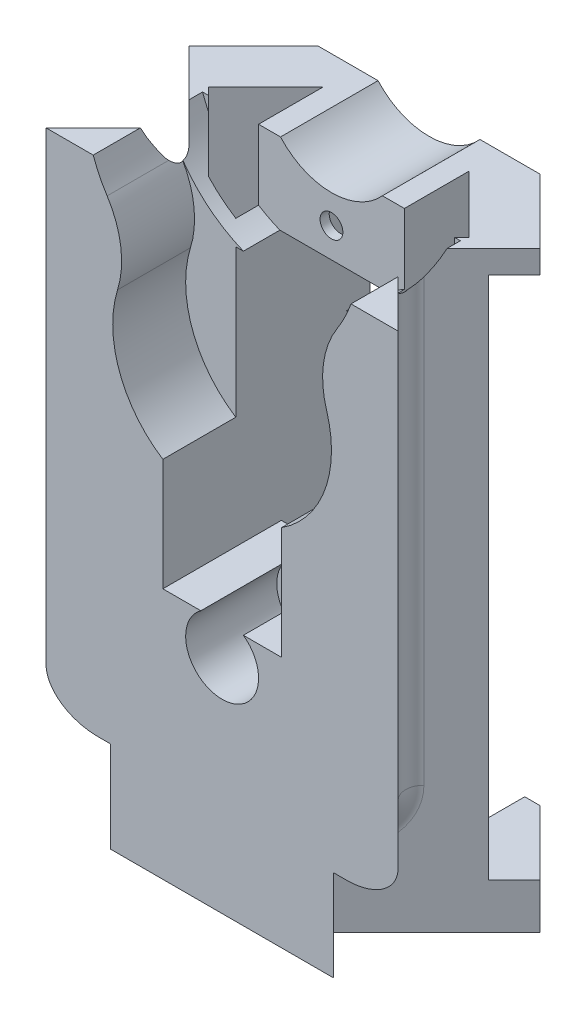
SolidWorks part; units mm, degrees
material "ABS"
ref_plane "前基準面" through (0, 0, 0) normal (0, 0, 1) x (1, 0, 0)
ref_plane "上基準面" through (0, 0, 0) normal (0, 1, 0) x (1, 0, 0)
ref_plane "右基準面" through (0, 0, 0) normal (1, 0, 0) x (0, 0, -1)
sketch "草圖1" plane through (0, 0, 0) normal (0, 1, 0) x (1, 0, 0)
  line L0 (0, 0) -> (24.34, 0)
  line L1 (24.34, 0) -> (34.67, -10.33)
  line L2 (34.67, -22.7) -> (-10.33, -22.7)
  line L3 (-10.33, -10.33) -> (0, 0)
  line L4 (-10.33, -22.7) -> (-10.33, -10.33)
  line L5 (34.67, -22.7) -> (34.67, -10.33)
  line L6 (12.17, 0) -> (12.17, -22.7) construction
  dimension "D1" = 22.7
  dimension "D2" = 24.34
  dimension "D3" = 45
extrude "填料-伸長1" add sketch "草圖1" along normal blind 65
ref_plane "平面1" through (0, 5, 0) normal (0, 1, 0) x (1, 0, 0)
sketch "草圖2" plane through (0, 5, 0) normal (0, 1, 0) x (1, 0, 0)
  line L0 (0, 0) -> (-22.7, -22.7)
  line L1 (-22.7, -22.7) -> (-17.0431, -22.7)
  line L2 (-10.33, -22.7) -> (34.67, -22.7) construction
  line L3 (-17.0431, -22.7) -> (5.6569, 0)
  line L4 (24.34, 0) -> (0, 0) construction
  line L5 (5.6569, 0) -> (0, 0)
  line L6 (-10.33, -22.7) -> (34.67, -22.7) construction
  line L8 (0, 0) -> (-10.33, -10.33) construction
  dimension "D1" = 4
extrude "除料-伸長1" cut sketch "草圖2" along normal blind 57.5
ref_plane "平面2" through (12.17, 0, 0) normal (-1, 0, 0) x (0, 0, 1)
mirror "鏡射1" about plane through (12.17, 0, 0) normal (-1, 0, 0) of "除料-伸長1"
sketch "草圖3" plane through (0, 0, 22.7) normal (0, 0, 1) x (1, 0, 0)
  line L0 (12.17, 65) -> (12.17, 0) construction
  line L1 (-10.33, 65) -> (34.67, 65) construction
  line L2 (-10.33, 0) -> (34.67, 0) construction
  point P6 (12.17, 50)
  point P8 (12.17, 70)
  dimension "D1" = 50
  dimension "D2" = 20
sketch "草圖4" plane through (0, 0, 22.7) normal (0, 0, 1) x (1, 0, 0)
  line L0 (12.17, 65) -> (12.17, 0) construction
  line L1 (5.67, 56.11) -> (18.67, 56.11)
  line L2 (5.67, 56.11) -> (5.67, 27.61)
  line L3 (5.67, 27.61) -> (18.67, 27.61)
  line L4 (18.67, 56.11) -> (18.67, 27.61)
  line L5 (5.67, 56.11) -> (18.67, 27.61) construction
  line L6 (5.67, 27.61) -> (18.67, 56.11) construction
  line L7 (12.17, 59.36) -> (12.17, 56.11) construction
  line L8 (12.17, 24.36) -> (12.17, 27.61) construction
  circle A0 centre (12.17, 59.36) radius 1.25
  circle A1 centre (12.17, 24.36) radius 1.25
  point P0 (12.17, 41.86)
  dimension "D5" = 2.5
  dimension "D1" = 28.5
  dimension "D2" = 13
  dimension "D3" = 6.11
  dimension "D4" = 35
extrude "除料-伸長2" cut sketch "草圖4" against normal blind 13
sketch "草圖9" plane through (0, 0, 9.7) normal (0, 0, 1) x (1, 0, 0)
  line L0 (12.17, 65) -> (12.17, 0) construction
  line L1 (5.67, 61.06) -> (18.67, 61.06)
  line L2 (5.67, 61.06) -> (5.67, 22.66)
  line L3 (5.67, 22.66) -> (18.67, 22.66)
  line L4 (18.67, 61.06) -> (18.67, 22.66)
  line L5 (5.67, 61.06) -> (18.67, 22.66) construction
  line L6 (5.67, 22.66) -> (18.67, 61.06) construction
  line L7 (18.67, 27.61) -> (18.67, 56.11) construction
  line L9 (18.67, 27.61) -> (18.67, 56.11) construction
  point P0 (12.17, 41.86)
  point P13 (18.67, 41.86)
  point P14 (18.67, 41.86)
  dimension "D1" = 38.4
extrude "除料-伸長6" cut sketch "草圖9" against normal through all
sketch "草圖10" plane through (0, 0, 0) normal (0, -1, 0) x (1, 0, 0)
  line L0 (24.34, 0) -> (0, 0) construction
  line L1 (20.67, 3) -> (3.67, 3)
  line L2 (22.67, 5) -> (22.67, 10)
  line L3 (22.67, 10) -> (1.67, 10)
  line L4 (1.67, 5) -> (1.67, 10)
  line L5 (12.17, 2.75) -> (12.17, -2.75) construction
  line L6 (22.67, 5) -> (20.67, 3)
  line L7 (3.67, 3) -> (1.67, 5)
  point P0 (22.67, 3)
  point P3 (1.67, 3)
  point P8 (12.17, 3)
  dimension "D1" = 21
  dimension "D2" = 3
  dimension "D3" = 7
extrude "除料-伸長7" cut sketch "草圖10" against normal blind 18
sketch "草圖13" plane through (0, 0, 0) normal (0, -1, 0) x (1, 0, 0)
  line L0 (1.67, 10) -> (1.67, 5) construction
  line L1 (22.67, 10) -> (1.67, 10)
  line L2 (22.67, 10) -> (22.67, 15)
  line L3 (22.67, 15) -> (1.67, 15)
  line L4 (1.67, 10) -> (1.67, 15)
extrude "除料-伸長10" cut sketch "草圖13" against normal blind 18
sketch "草圖11" plane through (0, 0, 0) normal (0, -1, 0) x (1, 0, 0)
  line L0 (-9.5579, 4.5842) -> (-25.1143, 20.1405)
  line L1 (-9.5579, 4.5842) -> (0.7071, 14.8492)
  line L2 (-25.1143, 20.1405) -> (-14.8492, 30.4056)
  line L3 (0.7071, 14.8492) -> (-14.8492, 30.4056)
  line L4 (0, 0) -> (-10.33, 10.33) construction
  line L7 (0, 0) -> (-10.33, 10.33) construction
  dimension "D2" = 22
  dimension "D3" = 11
  dimension "D4" = 10
extrude "除料-伸長8" cut sketch "草圖11" against normal through all
sketch "草圖12" plane through (0, 0, 0) normal (0, -1, 0) x (1, 0, 0)
  line L0 (-4.2426, 9.8995) -> (-19.799, 25.4558)
  line L1 (-4.2426, 9.8995) -> (4.2426, 18.3848)
  line L2 (-19.799, 25.4558) -> (-11.3137, 33.9411)
  line L3 (4.2426, 18.3848) -> (-11.3137, 33.9411)
  line L5 (-7.0711, 7.0711) -> (0.7071, 14.8492) construction
  line L7 (0.7071, 14.8492) -> (-7.1437, 22.7) construction
  dimension "D1" = 12
  dimension "D2" = 22
  dimension "D3" = 7
extrude "除料-伸長9" cut sketch "草圖12" against normal blind 10
fillet "圓角1" radius 4 1 edges at (-3.2183, 10, 18.7746)
mirror "鏡射3" about plane through (12.17, 0, 0) normal (-1, 0, 0) of "圓角1", "除料-伸長9", "除料-伸長8"
sketch "草圖21" plane through (0, 0, 0) normal (0, 0, -1) x (-1, 0, 0)
  line L0 (-1.67, 18) -> (-1.67, 0) construction
  line L1 (-22.67, 0) -> (-1.67, 0)
  line L2 (-22.67, 0) -> (-22.67, 14)
  line L3 (-22.67, 14) -> (-1.67, 14)
  line L4 (-1.67, 0) -> (-1.67, 14)
  line L7 (-24.34, 0) -> (0, 0) construction
  line L8 (-22.67, 5) -> (-22.67, 18) construction
  dimension "D1" = 14
extrude "除料-伸長17" cut sketch "草圖21" against normal blind 8
chamfer "導角2" [suppressed] distance 4 angle 45
sketch "草圖17" plane through (2.8284, 0, 2.8284) normal (-0.7071, 0, -0.7071) x (-0.7071, 0, 0.7071)
  line L1 (1.6383, 14) -> (21.437, 14)
  line L2 (1.6383, 14) -> (1.6383, 5)
  line L3 (1.6383, 5) -> (21.437, 5)
  line L4 (21.437, 14) -> (21.437, 5)
  line L5 (1.6383, 5) -> (1.6383, 14) construction
  line L6 (1.6383, 14) -> (-4, 14) construction
  dimension "D1" = 9
extrude "除料-伸長13" cut sketch "草圖17" against normal blind 3
sketch "草圖18" plane through (0, 0, 15) normal (0, 0, 1) x (1, 0, 0)
  line L0 (-0.0726, 0) -> (24.4126, 0) construction
  line L1 (19.17, 0) -> (5.17, 0)
  line L2 (19.17, 0) -> (19.17, 18)
  line L3 (19.17, 18) -> (5.17, 18)
  line L4 (5.17, 0) -> (5.17, 18)
  line L5 (12.17, 2.75) -> (12.17, -2.75) construction
  point P6 (12.17, 0)
  dimension "D1" = 18
  dimension "D2" = 14
extrude "除料-伸長14" cut sketch "草圖18" along normal blind 5
sketch "草圖19" plane through (0, 0, 22.7) normal (0, 0, 1) x (1, 0, 0)
  circle A0 centre (12.17, 24.36) radius 4
extrude "除料-伸長15" cut sketch "草圖19" against normal blind 10
fillet "圓角6" radius 2 6 edges at (3.8891, 10, 18.0312) (1.5355, 11.1716, 15.6777) (20.4509, 10, 18.0312) (22.8045, 11.1716, 15.6777) (0.7071, 39.5, 14.8492) (23.6329, 39.5, 14.8492)
sketch "草圖5" plane through (0, 0, 22.7) normal (0, 0, 1) x (1, 0, 0)
  line L0 (12.17, 65) -> (12.17, 0) construction
  circle A0 centre (12.17, 50) radius 12
  point P3 (12.17, 70)
  dimension "D1" = 24
  dimension "D2" = 20
extrude "除料-伸長3" cut sketch "草圖5" against normal blind 8 contours A0
sketch "草圖20" plane through (0, 18, 0) normal (0, -1, 0) x (1, 0, 0)
  line L0 (2.67, 8) -> (21.67, 8) construction
  line L1 (12.17, 2.75) -> (12.17, -2.75) construction
  line L2 (24.34, 0) -> (22.67, 0) construction
  line L3 (4.17, 3.6082) -> (-2.1213, 9.8995)
  line L4 (-2.1213, 9.8995) -> (1.1792, 13.2)
  line L5 (4.17, 13.2) -> (4.17, 3.6082)
  line L6 (5.67, 0) -> (5.67, 9.7) construction
  line L7 (-4.2426, 9.8995) -> (5.6569, 0) construction
  line L8 (-7.0711, 7.0711) -> (4.2426, 18.3848) construction
  line L12 (4.17, 13.2) -> (1.1792, 13.2)
  line L13 (20.17, 13.2) -> (23.1608, 13.2)
  line L14 (26.4613, 9.8995) -> (23.1608, 13.2)
  line L15 (20.17, 3.6082) -> (26.4613, 9.8995)
  line L16 (20.17, 13.2) -> (20.17, 3.6082)
  point P2 (12.17, 8)
  dimension "D1" = 1.5
  dimension "D2" = 19
  dimension "D3" = 8
  dimension "D4" = 1.5
  dimension "D5" = 1.5
  dimension "D6" = 1.5
extrude "除料-伸長16" cut sketch "草圖20" against normal through all
sketch "草圖22" plane through (0, 14, 0) normal (0, -1, 0) x (1, 0, 0)
  line L0 (1.4142, 16.2635) -> (-3.5223, 21.2)
  line L1 (-3.5223, 21.2) -> (3.67, 21.2)
  line L4 (-0.7071, 16.2635) -> (-7.1437, 22.7) construction
  line L5 (-0.0726, 22.7) -> (24.4126, 22.7) construction
  line L6 (3.67, 21.2) -> (3.67, 18.5192)
  line L7 (3.67, 18.5192) -> (1.4142, 16.2635)
  line L8 (22.0292, 34.05) -> (-23.3708, -11.35) construction
  line L9 (5.17, 20) -> (5.17, 15) construction
  line L10 (12.17, 2.75) -> (12.17, -2.75) construction
  line L11 (27.8623, 21.2) -> (20.67, 21.2)
  line L12 (22.9258, 16.2635) -> (27.8623, 21.2)
  line L13 (20.67, 18.5192) -> (22.9258, 16.2635)
  line L14 (20.67, 21.2) -> (20.67, 18.5192)
  dimension "D1" = 1.5
  dimension "D2" = 1.5
  dimension "D3" = 2
  dimension "D4" = 1.5
extrude "除料-伸長18" cut sketch "草圖22" against normal blind 25
sketch "草圖23" plane through (0, 18, 0) normal (0, -1, 0) x (1, 0, 0)
  line L0 (4.17, 13.2) -> (1.1792, 13.2)
  line L1 (1.1792, 13.2) -> (4.17, 16.1908)
  line L2 (4.17, 16.1908) -> (4.17, 13.2)
  line L3 (1.1792, 13.2) -> (-2.1213, 9.8995) construction
  line L4 (12.17, 2.75) -> (12.17, -2.75) construction
  line L5 (23.1608, 13.2) -> (20.17, 16.1908)
  line L6 (20.17, 13.2) -> (23.1608, 13.2)
  line L7 (20.17, 16.1908) -> (20.17, 13.2)
extrude "除料-伸長19" cut sketch "草圖23" against normal blind 20
sketch "草圖8" plane through (0, 0, 22.7) normal (0, 0, 1) x (1, 0, 0)
  line L0 (4.67, 70) -> (4.67, 73.8373)
  line L1 (4.67, 73.8373) -> (19.67, 73.8373)
  line L2 (19.67, 73.8373) -> (19.67, 70)
  arc A0 (4.67, 70) -> (19.67, 70) centre (12.17, 70) ccw
  dimension "D1" = 15
extrude "除料-伸長5" cut sketch "草圖8" against normal through all contours L0 L1 L2 A0
sketch "草圖7" plane through (0, 0, 22.7) normal (0, 0, 1) x (1, 0, 0)
  line L4 (-2.83, 70) -> (27.17, 70)
  arc A0 (-2.83, 70) -> (27.17, 70) centre (12.17, 70) ccw
  dimension "D1" = 30
extrude "除料-伸長20" cut sketch "草圖7" against normal blind 12
fillet "圓角5" radius 10 2 edges at (21.1366, 57.975, 18.7) (3.2034, 57.975, 18.7)
